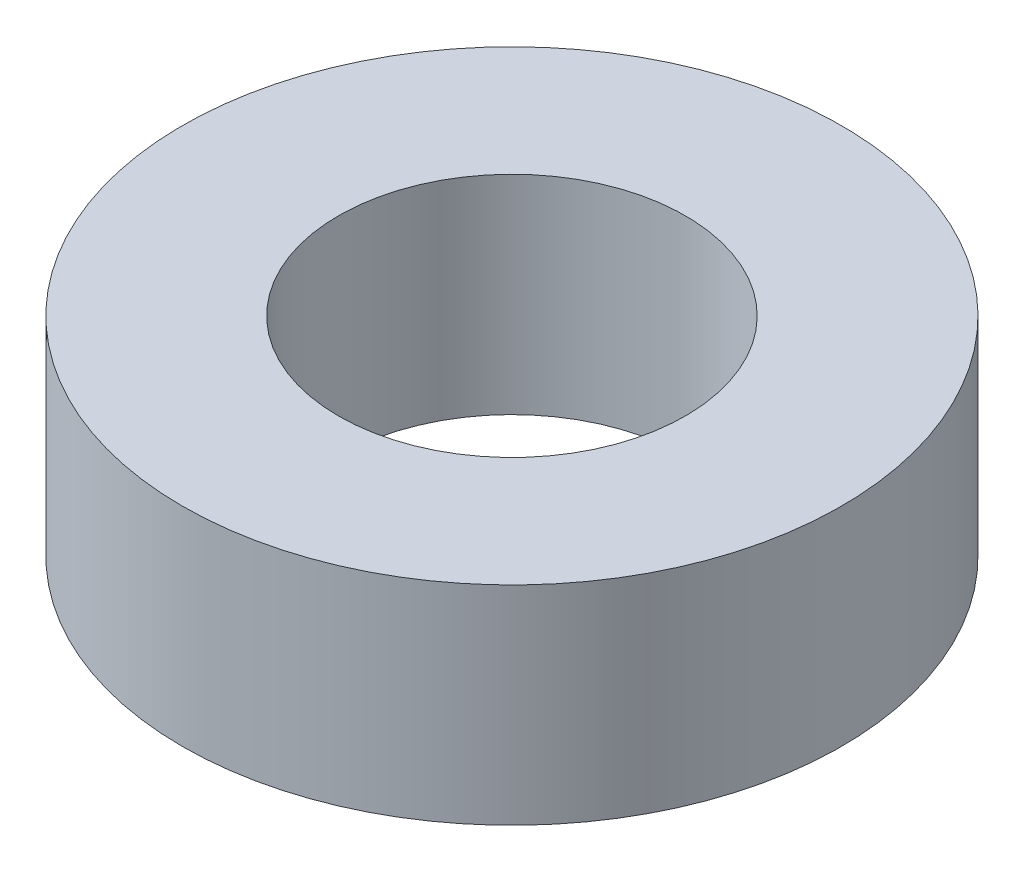
SolidWorks part; units mm, degrees
ref_plane "Front plane" through (0, 0, 0) normal (0, 0, 1) x (1, 0, 0)
ref_plane "Top plane" through (0, 0, 0) normal (0, 1, 0) x (1, 0, 0)
ref_plane "Right plane" through (0, 0, 0) normal (1, 0, 0) x (0, 0, -1)
ref_axis "Axis X" through (0, 0, 0) along (1, 0, 0)
ref_axis "Axis Y" through (0, 0, 0) along (0, 1, 0)
ref_axis "Axis Z" through (0, 0, 0) along (0, 0, 1)
sketch "Sketch1" plane through (0, 0, 0) normal (0, 1, 0) x (1, 0, 0)
  circle A0 centre (0, 0) radius 4.75
  dimension "D1" = 9.5
extrude "Extrude1" add sketch "Sketch1" along normal blind 3
sketch "Sketch2" plane through (0, 3, 0) normal (0, 1, 0) x (1, 0, 0)
  circle A0 centre (0, 0) radius 2.5
  dimension "D1" = 5
extrude "Extrude2" cut sketch "Sketch2" against normal through all
equation "\"motor_D\"= 40'Motor diameter"
equation "\"motor_H\"= 18'Motor heigh"
equation "\"motor_d1\"= 28'Seating diameter of screws on the fixed part of the motor"
equation "\"motor_s1\"= 3'Screws diameter on the fixed part of motor"
equation "\"motor_a2\"= 10'Seating parameter in rectangle of screws on the moving part of the motor"
equation "\"motor_s2\"= 3'Screws diameter on the moving part of motor"
equation "\"motor_Dc\"= 10'Central hole diameter of motor"
equation "\"bearing_d1\"= 8'Bearing inner diameter"
equation "\"bearing_d2\"= 16'Bearing external diameter"
equation "\"bearing h\"= 5'Bearing heigh"
equation "\"pin_d\"= 2'Pin diameter"
equation "\"pin_h\"= 12'Pin heigh"
equation "\"magnet_d1\"= 5'Magnet inner diameter"
equation "\"magnet_d2\"= 9.5'Magnet external diameter"
equation "\"magnet_h\"= 3'Magnet heigh"
equation "\"motor_b2\"= 22'Seating parameter in rectangle of screws on the moving part of the motor"
equation "\"motor_d2\"= 30.5'Seating diameter of screws on the moving part of the motor (if this parameter is not determine, write 0)"
equation "\"motor_cmd\"= 13'Central magnet mount diameter"
equation "\"motor_cmh\"= 0'Central magnet mount heigh (if not write 0)"
equation "\"motor_whR\"= 17.3'Distance from center of motor to wires"
equation "\"D1@Sketch1\"=\"magnet_d2\""
equation "\"D1@Extrude1\"=\"magnet_h\""
equation "\"D1@Sketch2\"=if( \"magnet_d1\"=0,1,\"magnet_d1\")"
equation "\"Extrude2\"= IIF ( \"magnet_d1\" = 0 , \"suppressed\" , \"unsuppressed\" )"
